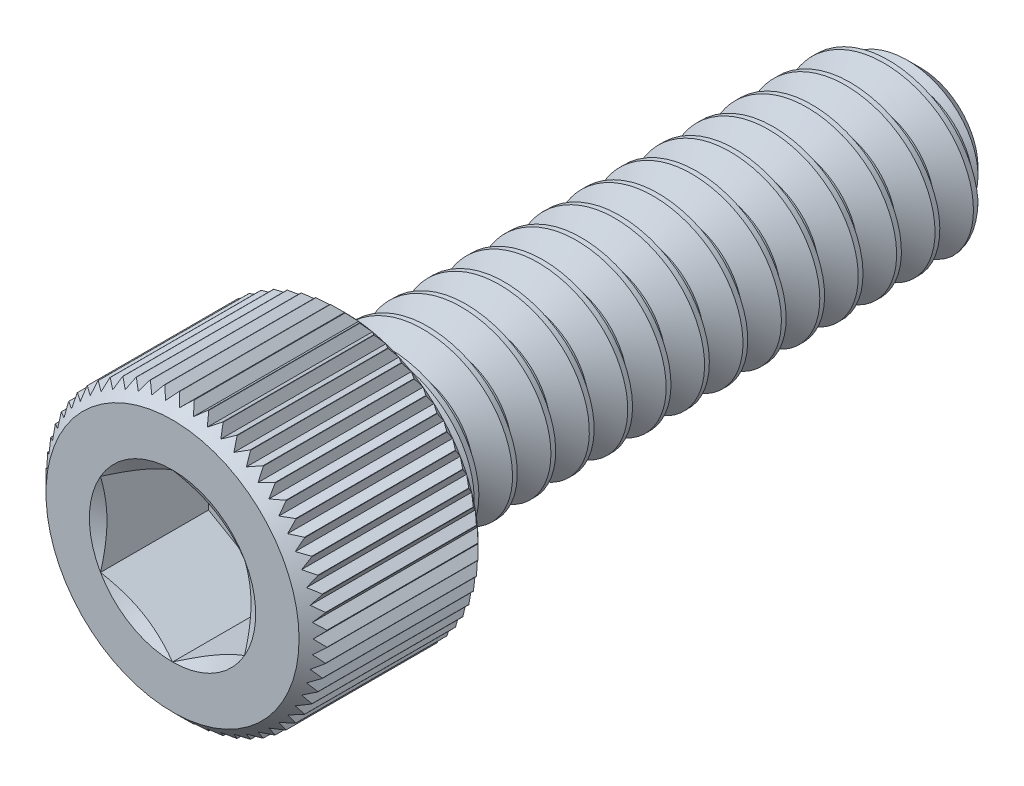
SolidWorks part; units mm, degrees
ref_plane "Front Plane" through (0, 0, 0) normal (0, 0, 1) x (1, 0, 0)
ref_plane "Top Plane" through (0, 0, 0) normal (0, 1, 0) x (1, 0, 0)
ref_plane "Right Plane" through (0, 0, 0) normal (1, 0, 0) x (0, 0, -1)
sketch "Sketch1" plane through (0, 0, 0) normal (1, 0, 0) x (0, 0, -1)
  line L0 (6.1849, 0) -> (-6.1849, 0) construction
  line L1 (-6.1849, 0) -> (-6.1849, 2.3241) construction
  line L2 (-3.3401, 1.4224) -> (-3.3401, 0) construction
  line L3 (5.5499, 0) -> (5.5499, 0.635) construction
  line L4 (-3.3401, 0) -> (-3.3401, -1.4224) construction
  point P6 (-6.1849, 1.1906)
  point P9 (-6.1849, -1.1906)
  point P10 (-3.3401, 0)
  point P13 (3.9624, -1.4224)
  dimension "Head Dia" = 4.6482
  dimension "Head Height" = 2.8448
  dimension "Thread OD" = 2.8448
  dimension "Pitch" = 0.635
  dimension "drive Size" = 2.3813
  dimension "D1" = 0.635
  dimension "D2" = 2.2225
sketch "Sketch2" plane through (0, 0, 0) normal (1, 0, 0) x (0, 0, -1)
  line L0 (6.1849, 0.9461) -> (5.7086, 1.4224)
  line L1 (-6.1849, 2.3241) -> (-3.3401, 2.3241)
  line L2 (-6.1849, 2.3241) -> (-6.1849, 0)
  line L4 (-3.3401, 2.3241) -> (-3.3401, 1.4224)
  line L5 (-3.3401, 1.4224) -> (5.7086, 1.4224)
  line L8 (6.1849, 0.9461) -> (6.1849, 0)
  line L9 (6.1849, 0) -> (-6.1849, 0) construction
  line L10 (6.1849, 0) -> (-6.1849, 0)
  dimension "D1" = 135
  dimension "D2" = 0.4763
revolve "Revolve1" add sketch "Sketch2" angle 360 about L10
sketch "Sketch4" plane through (0, 0, 6.1849) normal (0, 0, 1) x (1, 0, 0)
  line L1 (0, 1.3748) -> (-1.1906, 0.6874)
  line L2 (-1.1906, 0.6874) -> (-1.1906, -0.6874)
  line L3 (-1.1906, -0.6874) -> (0, -1.3748)
  line L4 (0, -1.3748) -> (1.1906, -0.6874)
  line L5 (1.1906, -0.6874) -> (1.1906, 0.6874)
  line L6 (1.1906, 0.6874) -> (0, 1.3748)
  circle A0 centre (0, 0) radius 1.1906 construction
  circle A1 centre (0, 0) radius 2.3241 construction
  circle A2 centre (0, 0) radius 2.3241 construction
  dimension "D1" = 2.3813
extrude "Cut-Extrude1" cut sketch "Sketch4" against normal blind 1.7859
sketch "Sketch5" plane through (0, 0, 6.1849) normal (0, 0, 1) x (1, 0, 0)
  circle A0 centre (0, 0) radius 1.3748
extrude "Cut-Extrude2" cut sketch "Sketch5" against normal blind 10 draft 60
chamfer "Chamfer1" distance 0.2324 angle 45 1 edges at (-2.3241, 0, 6.1849)
chamfer "Chamfer2" distance 0.1162 angle 45 1 edges at (-2.3241, 0, 3.3401)
sketch "Sketch3" plane through (0, 0, -6.1849) normal (0, 0, -1) x (-1, 0, 0)
  circle A0 centre (0, 0) radius 1.4224 construction
  circle A1 centre (0, 0) radius 1.4224
split "Split1" bodies to split 106 resulting bodies 114 115 split by face at (-2.2079, 0, 3.3401)
curve "Helix/Spiral1" pitch 0.635 height 10.16 radius 1.4224 centre (0, 0, -6.1849) axis (0, 0, 1) start towards (0, 1, 0)
sketch "Sketch7" plane through (0, 0, 0) normal (1, 0, 0) x (0, 0, -1)
  line L0 (6.1452, 1.4911) -> (6.4627, 0.9412) construction
  line L1 (6.4627, 0.9412) -> (6.7802, 1.4911) construction
  line L2 (6.7802, 1.4911) -> (6.1452, 1.4911) construction
  line L3 (6.1849, 1.4224) -> (6.7405, 1.4224)
  line L4 (6.4627, 1.4911) -> (6.4627, 1.4224) construction
  line L5 (6.4627, 1.4224) -> (6.4627, 1.01) construction
  line L6 (6.4627, 1.01) -> (6.4627, 0.9412) construction
  line L7 (6.423, 1.01) -> (6.5024, 1.01)
  line L8 (6.1651, 1.4568) -> (6.7604, 1.4568) construction
  line L9 (6.5024, 1.01) -> (6.7405, 1.4224)
  line L10 (6.423, 1.01) -> (6.1849, 1.4224)
  point P0 (6.4627, 1.4568)
  dimension "D1" = 0.635
  dimension "D2" = 0.0794
sweep "Cut-Sweep1" cut profiles "Sketch7" path "Helix/Spiral1" align with end faces yes
sketch "Sketch11" plane through (0, 0, 3.3401) normal (0, 0, -1) x (-1, 0, 0)
  circle A0 centre (0, 0) radius 1.4911
extrude "Boss-Extrude4" add sketch "Sketch11" along normal up to vertex (9.525 mm away) draft 45 up to point (0, 0, -6.1849)
sketch "Sketch9" plane through (0, 0, 3.3401) normal (0, 0, -1) x (-1, 0, 0)
  line L0 (0, 0) -> (0, 2.3241) construction
  line L1 (0, 2.2079) -> (-0.2436, 2.4403)
  line L2 (-0.2436, 2.4403) -> (0.2436, 2.4403)
  line L3 (0.2436, 2.4403) -> (0, 2.2079)
  line L4 (-0.1218, 2.3241) -> (0, 0) construction
  line L5 (0, 0) -> (0.1218, 2.3241) construction
  circle A0 centre (0, 0) radius 2.3241 construction
  circle A1 centre (0, 0) radius 2.2079 construction
  dimension "D1" = 0.2324
  dimension "D2" = 6
extrude "Cut-Extrude3" cut sketch "Sketch9" against normal up to next
pattern_circular "CirPattern1" count 60 over 360 about axis through (0, 0, 3.3401) along (0, 0, -1) of "Cut-Extrude3"
equation "\"D1@Sketch1\"=\"Pitch@Sketch1\""
equation "\"D2@Sketch2\"=\"D1@Sketch1\"*.75"
equation "\"D4@Helix/Spiral1\"=\"Pitch@Sketch1\""
equation "\"D3@Helix/Spiral1\"=\"Length@Sketch1\"+\"Pitch@Sketch1\""
equation "\"D1@Sketch4\"=\"drive Size@Sketch1\""
equation "\"D1@Cut-Extrude1\"=\"D1@Sketch4\"*.75"
equation "\"D19\"= \"D1@Sketch4\" * .75"
equation "\"D1@Chamfer1\" = \"Head Dia@Sketch1\" * .05"
equation "\"D1@Chamfer2\"=\"D1@Chamfer1\"/2"
equation "\"D2@Sketch7\"=\"D1@Sketch7\"/8"
equation "\"D1@Sketch7\"=\"D4@Helix/Spiral1\""
equation "\"D2@Sketch1\"=\"Pitch@Sketch1\"*3.5"
equation "\"D1@Sketch9\"=\"D1@Chamfer1\""
equation "\"D1@CirPattern1\"=\"D3@CirPattern1\"/\"D2@Sketch9\""
